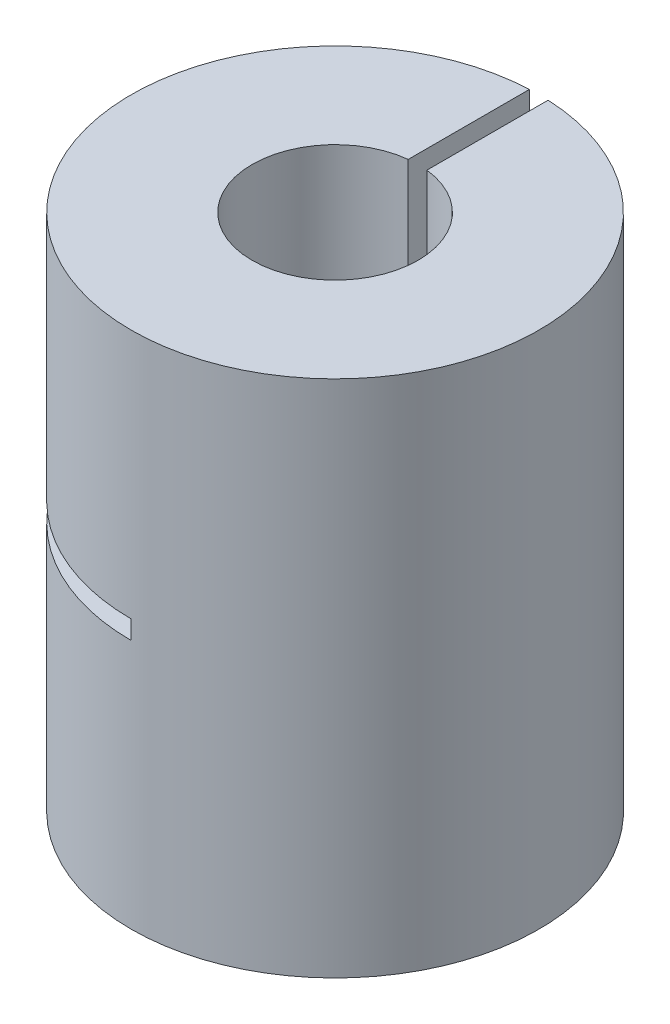
SolidWorks part; units mm, degrees
ref_plane "Alzado" through (0, 0, 0) normal (0, 0, 1) x (1, 0, 0)
ref_plane "Planta" through (0, 0, 0) normal (0, 1, 0) x (1, 0, 0)
ref_plane "Vista lateral" through (0, 0, 0) normal (1, 0, 0) x (0, 0, -1)
sketch "Sketch1" plane through (0, 0, 0) normal (0, 1, 0) x (1, 0, 0)
  circle A0 centre (0, 0) radius 9.825
  circle A1 centre (0, 0) radius 2.505
  dimension "D1" = 19.65
  dimension "D2" = 5.01
extrude "Boss-Extrude1" add sketch "Sketch1" along normal blind 25
sketch "Sketch2" plane through (0, 25, 0) normal (0, 1, 0) x (1, 0, 0)
  circle A0 centre (0, 0) radius 4
  dimension "D1" = 8
extrude "Cut-Extrude1" cut sketch "Sketch2" against normal blind 13.5
sketch "Sketch3" plane through (0, 0, 0) normal (0, 0, 1) x (1, 0, 0)
  line L0 (-9.825, 25) -> (-9.825, 0) construction
  line L1 (-9.825, 0) -> (9.825, 0) construction
  line L4 (-9.825, 12.5) -> (-9.825, 12.95)
  line L5 (-9.825, 12.95) -> (0, 12.95)
  line L6 (0, 12.5) -> (0, 12.95)
  line L8 (-9.825, 12.5) -> (-9.825, 12.05)
  line L9 (-9.825, 12.05) -> (0, 12.05)
  line L10 (0, 12.5) -> (0, 12.05)
  dimension "D1" = 0.45
  dimension "D2" = 0.45
  dimension "D3" = 9.825
extrude "Cut-Extrude2" cut sketch "Sketch3" against normal blind 13.5 and the other way blind 13.5 contours L4 L5 L6 L10 L9 L8
sketch "Sketch5" plane through (0, 0, 0) normal (0, 0, 1) x (1, 0, 0)
  line L0 (9.825, 25) -> (-9.825, 25) construction
  line L1 (0, 0) -> (-0.45, 0)
  line L3 (0, 25) -> (-0.45, 25)
  line L4 (-0.45, 0) -> (-0.45, 25)
  line L6 (0, 0) -> (0.45, 0)
  line L8 (0, 25) -> (0.45, 25)
  line L9 (0.45, 0) -> (0.45, 25)
  dimension "D1" = 0.45
  dimension "D2" = 0.45
extrude "Cut-Extrude3" cut sketch "Sketch5" against normal blind 13.5
